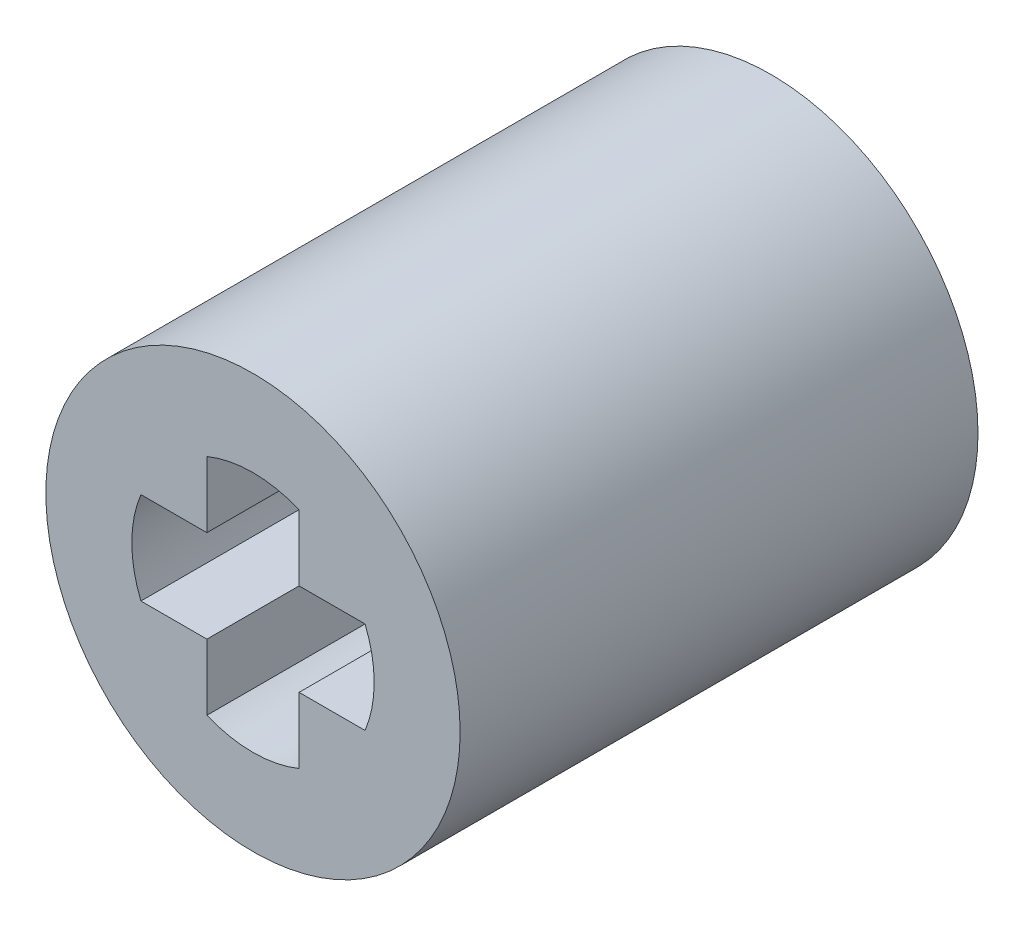
SolidWorks part; units mm, degrees
ref_plane "Front Plane" through (0, 0, 0) normal (0, 0, 1) x (1, 0, 0)
ref_plane "Top Plane" through (0, 0, 0) normal (0, 1, 0) x (1, 0, 0)
ref_plane "Right Plane" through (0, 0, 0) normal (1, 0, 0) x (0, 0, -1)
sketch "Sketch1" plane through (0, 0, 0) normal (0, 0, 1) x (1, 0, 0)
  line L0 (-0.89, 2.1641) -> (-0.89, -2.1641)
  line L2 (0.89, -2.1641) -> (0.89, 2.1641)
  line L4 (-1.118, 1) -> (1.118, 1)
  line L5 (-2.1641, 0.89) -> (2.1641, 0.89)
  line L7 (-2.1641, -0.89) -> (2.1641, -0.89)
  circle A0 centre (0, 0) radius 2.34
  circle A1 centre (0, 0) radius 1.5
  circle A2 centre (0, 0) radius 4
  dimension "D1" = 4.68
  dimension "D3" = 3
  dimension "D8" = 8
  dimension "D2" = 1.78
  dimension "D4" = 1
  dimension "D5" = 1.78
  dimension "D6" = 0.89
  dimension "D7" = 0.89
extrude "Boss-Extrude1" add sketch "Sketch1" along normal blind 5 contours A2 A0 | A1 L0 A0 L5 | A1 L5 A0 L2 | L4 A1 L5 L0 | L0 A1 L4 | L4 A1 L2 | L5 A1 L4 L2 | L2 A1 L7 | A1 L2 A0 L7 | A1 L7 A0 L0 | L7 A1 L0 region at (-1.3916, 1.3916, 0) region at (-0.9686, 1.0715, 0) region at (1.3916, 1.3916, 0) region at (-1.0283, 0.942, 0) region at (0.9686, 1.0715, 0) region at (-1.3916, -1.3916, 0) region at (1.0283, 0.942, 0) region at (-1.0011, -1.0011, 0) region at (1.3916, -1.3916, 0) region at (1.0011, -1.0011, 0) region at (-3.8869, 0, 0)
extrude "Boss-Extrude2" add sketch "Sketch1<3>" against normal blind 5 contours A2 A0 | A1 L2 A0 L7 | A1 L7 A0 L5 | A1 L5 A0 L2 | A1 L2 A0 L0 | A1 L0 A0 L5 | A1 L5 A0 L7 | A1 L7 A0 L0 | L4 A1 L2 | L2 A1 L0 L4 | L0 A1 L4 | A1 L0 A0 L2 region at (0, 1.8418, 0) region at (-1.3916, 1.3916, 0) region at (0, 1.2124, 0) region at (-0.9686, 1.0715, 0) region at (1.3916, 1.3916, 0) region at (-1.8418, 0, 0) region at (0.9686, 1.0715, 0) region at (1.8418, 0, 0) region at (-1.3916, -1.3916, 0) region at (0, -1.8418, 0) region at (1.3916, -1.3916, 0) region at (-3.8869, 0, 0)
sketch "Sketch1<3>" plane through (0, 0, 0) normal (0, 0, 1) x (1, 0, 0) same geometry as "Sketch1"
